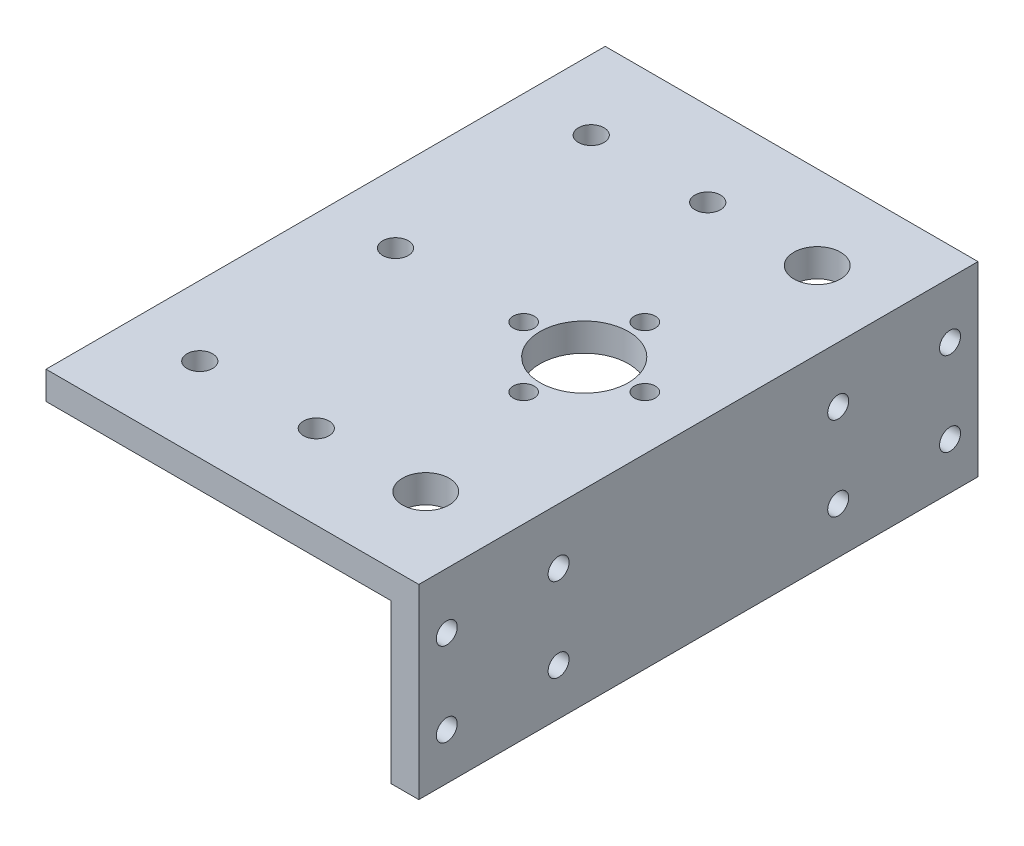
SolidWorks part; units mm, degrees
material "Lega 1060"
ref_plane "Piano frontale" through (0, 0, 0) normal (0, 0, 1) x (1, 0, 0)
ref_plane "Piano superiore" through (0, 0, 0) normal (0, 1, 0) x (1, 0, 0)
ref_plane "Piano destro" through (0, 0, 0) normal (1, 0, 0) x (0, 0, -1)
sketch "Schizzo1" plane through (0, 0, 0) normal (0, 0, 1) x (1, 0, 0)
  line L0 (0, 0) -> (-80, 0)
  line L1 (-80, 0) -> (-80, -6)
  line L2 (-80, -6) -> (-6, -6)
  line L3 (-6, -6) -> (-6, -40)
  line L4 (-6, -40) -> (0, -40)
  line L5 (0, -40) -> (0, 0)
  dimension "D1" = 80
  dimension "D2" = 40
  dimension "D3" = 6
  dimension "D4" = 6
extrude "Estrusione-Estrusione1" add sketch "Schizzo1" along normal blind 120
sketch "Schizzo2" plane through (-6, 0, 0) normal (-1, 0, 0) x (0, 0, 1)
  line L0 (120, -6) -> (0, -6) construction
  line L1 (0, -6) -> (0, -40) construction
  line L2 (120, -6) -> (120, -40) construction
  line B0 (90, -12) -> (114, -12) construction
  line B1 (114, -12) -> (114, -30) construction
  line B2 (114, -30) -> (90, -30) construction
  line B3 (90, -30) -> (90, -12) construction
  line B4 (6, -12) -> (30, -12) construction
  line B5 (30, -12) -> (30, -30) construction
  line B6 (30, -30) -> (6, -30) construction
  line B7 (6, -30) -> (6, -12) construction
  dimension "D1" = 6
  dimension "D2" = 6
  dimension "D3" = 6
sketch_block_instance "cuscinetti lineari-1"
sketch_block "cuscinetti lineari"
sketch_block_instance "cuscinetti lineari-2"
hole_wizard "Foro per Vite M4-1" positions "Schizzo4" profile "Schizzo3" hole size "M4" standard "ISO" end condition up to next
sketch "Schizzo4" plane through (-6, 0, 0) normal (-1, 0, 0) x (0, 0, 1)
  point P0 (6, -12)
  point P3 (30, -12)
  point P6 (30, -30)
  point P9 (6, -30)
  point P12 (90, -12)
  point P15 (90, -30)
  point P18 (114, -12)
  point P21 (114, -30)
sketch "Schizzo3" plane through (-6, -12, 6) normal (0, 1, 0) x (0, 0, 1)
  line L0 (0, 0) -> (0, 6)
  line L1 (0, 6) -> (2.25, 6)
  line L2 (2.25, 6) -> (2.25, 0)
  line L5 (2.25, 0) -> (0, 0)
  line L11 (0, -6.35) -> (0, 107.95) construction
  dimension "Thru Hole Dia." = 4.5
  dimension "Thru Hole Depth" = 6
sketch "Schizzo6" plane through (0, 0, 0) normal (0, 1, 0) x (1, 0, 0)
  line L0 (-16.5, -0.5808) -> (-16.5, -110.5835) construction
  line L2 (0, 0) -> (-80, 0) construction
  line L3 (-32.5218, -60) -> (-8.0464, -60) construction
  line L6 (0, -120) -> (-80, -120) construction
  circle A0 centre (-16.5, -18) radius 5
  circle A1 centre (-16.5, -102) radius 5
  dimension "D2" = 10
  dimension "D1" = 10.5
  dimension "D3" = 18
extrude "Taglio-Estrusione2" cut sketch "Schizzo6" against normal up to next
sketch "Schizzo7" plane through (0, 0, 0) normal (0, 1, 0) x (1, 0, 0)
  line L0 (-53.636, -60) -> (3.6289, -60) construction
  line L1 (0, -120) -> (-80, -120) construction
  line L2 (0, 0) -> (-80, 0) construction
  line L3 (-16.5, -18) -> (-16.5, -102) construction
  circle A0 centre (-24.5, -60) radius 9.5
  dimension "D1" = 19
  dimension "D2" = 8
extrude "Taglio-Estrusione3" cut sketch "Schizzo7" against normal up to next
hole_wizard "Foro per Vite M4-2" positions "Schizzo9" profile "Schizzo8" hole size "M4" standard "ISO" end condition through all
sketch "Schizzo9" plane through (0, 0, 0) normal (0, 1, 0) x (1, 0, 0)
  line L0 (-18.4657, -60) -> (-11.5, -60) construction
  line L2 (-24.5, -57.7684) -> (-24.5, -66.5063) construction
  circle A2 centre (-24.5, -60) radius 9.5 construction
  point P0 (-24.5, -47)
  point P2 (-37.5, -60)
  point P4 (-24.5, -73)
  point P8 (-11.5, -60)
  point P20 (-24.5, -60)
  dimension "D1" = 26
  dimension "D2" = 13
  dimension "D3" = 13
sketch "Schizzo8" plane through (-24.5, 0, 47) normal (1, 0, 0) x (0, 0, 1)
  line L0 (0, 0) -> (0, 40)
  line L1 (0, 40) -> (2.25, 40)
  line L2 (2.25, 40) -> (2.25, 0)
  line L5 (2.25, 0) -> (0, 0)
  line L11 (0, -6.35) -> (0, 107.95) construction
  dimension "Thru Hole Dia." = 4.5
  dimension "Thru Hole Depth" = 40
hole_wizard "Foro per Vite M5-1" positions "Schizzo11" profile "Schizzo10" hole size "M5" standard "ISO"
sketch "Schizzo11" plane through (0, -6, 0) normal (0, -1, 0) x (-1, 0, 0)
  line L0 (40, -18) -> (40, -102) construction
  line L2 (65, -60) -> (40, -60) construction
  line L3 (80, 0) -> (6, 0) construction
  line L4 (80, -120) -> (6, -120) construction
  line L5 (40, -18) -> (33.6884, -18) construction
  line L7 (80, -120) -> (80, 0) construction
  line L8 (65, -78.9835) -> (65, -42.6563) construction
  point P0 (40, -18)
  point P2 (65, -60)
  point P4 (40, -102)
  point P26 (65, -102)
  point P28 (65, -18)
  dimension "D1" = 40
  dimension "D2" = 15
  dimension "D3" = 84
sketch "Schizzo10" plane through (-40, -6, 18) normal (1, 0, 0) x (0, 0, -1)
  line L0 (0, 0) -> (0, 9.6524)
  line L1 (0, 9.6524) -> (2.75, 8)
  line L2 (2.75, 8) -> (2.75, 0)
  line L5 (2.75, 0) -> (0, 0)
  line L10 (0, 9.6524) -> (-2.75, 8) construction
  line L11 (0, -6.35) -> (0, 107.95) construction
  dimension "Hole Dia." = 5.5
  dimension "Hole Depth" = 8
  dimension "Drill Angle" = 118
